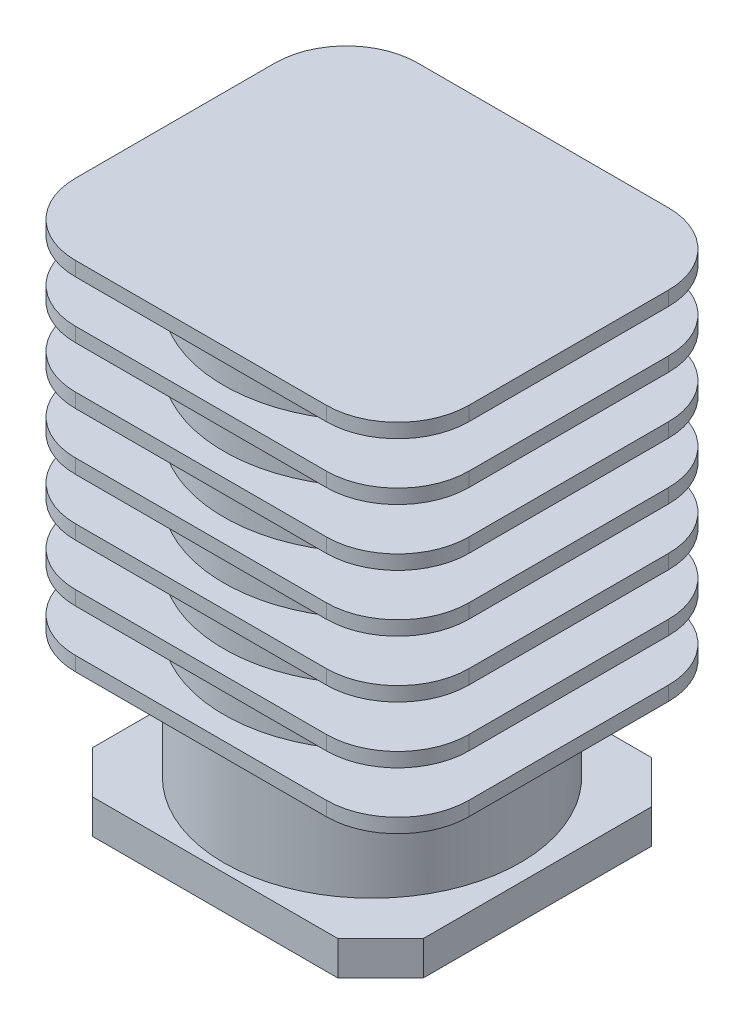
SolidWorks part; units mm, degrees
ref_plane "Front Plane" through (0, 0, 0) normal (0, 0, 1) x (1, 0, 0)
ref_plane "Top Plane" through (0, 0, 0) normal (0, 1, 0) x (1, 0, 0)
ref_plane "Right Plane" through (0, 0, 0) normal (1, 0, 0) x (0, 0, -1)
sketch "Sketch1" plane through (0, 0, 0) normal (0, 1, 0) x (1, 0, 0)
  circle A0 centre (0, 0) radius 52
extrude "Boss-Extrude1" add sketch "Sketch1" against normal blind 165
sketch "Sketch2" plane through (0, 0, 0) normal (0, 1, 0) x (1, 0, 0)
  line L1 (-44, -60) -> (44, -60)
  line L2 (-69, -35) -> (-69, 35)
  line L3 (-44, 60) -> (44, 60)
  line L4 (69, -35) -> (69, 35)
  line L5 (-69, -60) -> (69, 60) construction
  line L6 (-69, 60) -> (69, -60) construction
  arc A0 (-44, -60) -> (-69, -35) centre (-44, -35) cw
  arc A1 (44, -60) -> (69, -35) centre (44, -35) ccw
  arc A2 (44, 60) -> (69, 35) centre (44, 35) cw
  arc A3 (-69, 35) -> (-44, 60) centre (-44, 35) cw
  point P0 (0, 0)
  dimension "D3" = 25
  dimension "D1" = 138
  dimension "D2" = 120
extrude "Boss-Extrude2" add sketch "Sketch2" against normal blind 5
pattern_linear "LPattern1" count 7 spacing 20 along (0, -1, 0) of "Boss-Extrude2"
sketch "Sketch3" plane through (0, -165, 0) normal (0, -1, 0) x (1, 0, 0)
  line L0 (-43, 55) -> (-58, 40)
  line L1 (-43, -55) -> (43, -55)
  line L7 (-58, -40) -> (-58, 40)
  line L8 (-43, 55) -> (43, 55)
  line L13 (58, -40) -> (58, 40)
  line L16 (-43, -55) -> (-58, -40)
  line L17 (43, -55) -> (58, -40)
  line L18 (43, 55) -> (58, 40)
  point P0 (0, 0)
extrude "Boss-Extrude3" add sketch "Sketch3" along normal blind 12
